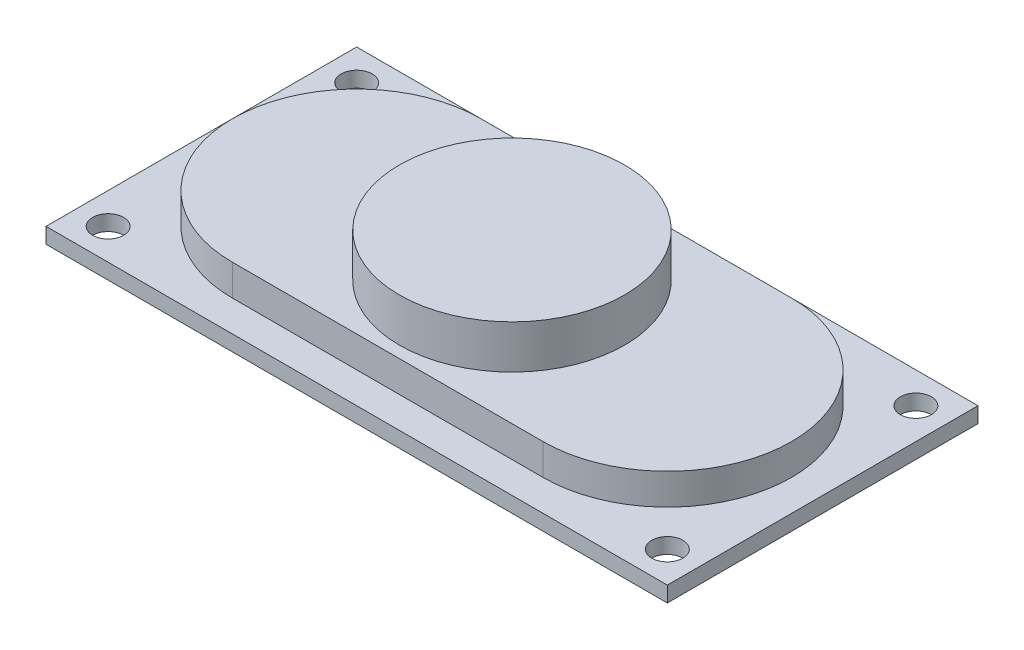
SolidWorks part; units mm, degrees
ref_plane "前视基准面" through (0, 0, 0) normal (0, 0, 1) x (1, 0, 0)
ref_plane "上视基准面" through (0, 0, 0) normal (0, 1, 0) x (1, 0, 0)
ref_plane "右视基准面" through (0, 0, 0) normal (1, 0, 0) x (0, 0, -1)
sketch "草图1" plane through (0, 0, 0) normal (0, 1, 0) x (1, 0, 0)
  line L0 (-49.2199, 0) -> (35.7447, 0) construction
  line L1 (-20, 10) -> (20, 10)
  line L2 (-20, 10) -> (-20, -10)
  line L3 (-20, -10) -> (20, -10)
  line L4 (20, 10) -> (20, -10)
  line L5 (0, 29.7163) -> (0, -24.7518) construction
  dimension "D1" = 20
  dimension "D2" = 40
extrude "凸台-拉伸1" add sketch "草图1" along normal blind 1
sketch "草图2" plane through (0, 1, 0) normal (0, 1, 0) x (1, 0, 0)
  line L0 (0, 12.9654) -> (0, -14.2708) construction
  line L1 (-24.1506, 0) -> (28.3042, 0) construction
  circle A0 centre (-18, 8) radius 1
  circle A1 centre (18, 8) radius 1
  circle A2 centre (18, -8) radius 1
  circle A3 centre (-18, -8) radius 1
  point P15 (-13.4697, 10.6512)
  dimension "D1" = 2
  dimension "D2" = 16
  dimension "D3" = 36
extrude "切除-拉伸1" cut sketch "草图2" against normal blind 1
sketch "草图3" plane through (0, 1, 0) normal (0, 1, 0) x (1, 0, 0)
  line L0 (-10, 0) -> (10, 0) construction
  line L1 (-10, 8) -> (10, 8)
  line L2 (-10, -8) -> (10, -8)
  line L3 (0, 12.906) -> (0, -13.1434) construction
  arc A0 (-10, 8) -> (-10, -8) centre (-10, 0) ccw
  arc A1 (10, -8) -> (10, 8) centre (10, 0) ccw
  point P3 (0, 0)
  point P10 (0, 0)
  dimension "D1" = 20
  dimension "D2" = 16
extrude "凸台-拉伸2" add sketch "草图3" along normal blind 2
shell "抽壳2" thickness 1 removed face at (18, 0, -9)
sketch "草图4" plane through (0, 3, 0) normal (0, 1, 0) x (1, 0, 0)
  circle A0 centre (0, 0) radius 7.25
  dimension "D1" = 14.5
extrude "凸台-拉伸3" add sketch "草图4" along normal offset from surface (2.8 mm away) 5.8 up to face at (0, 0, 0)
